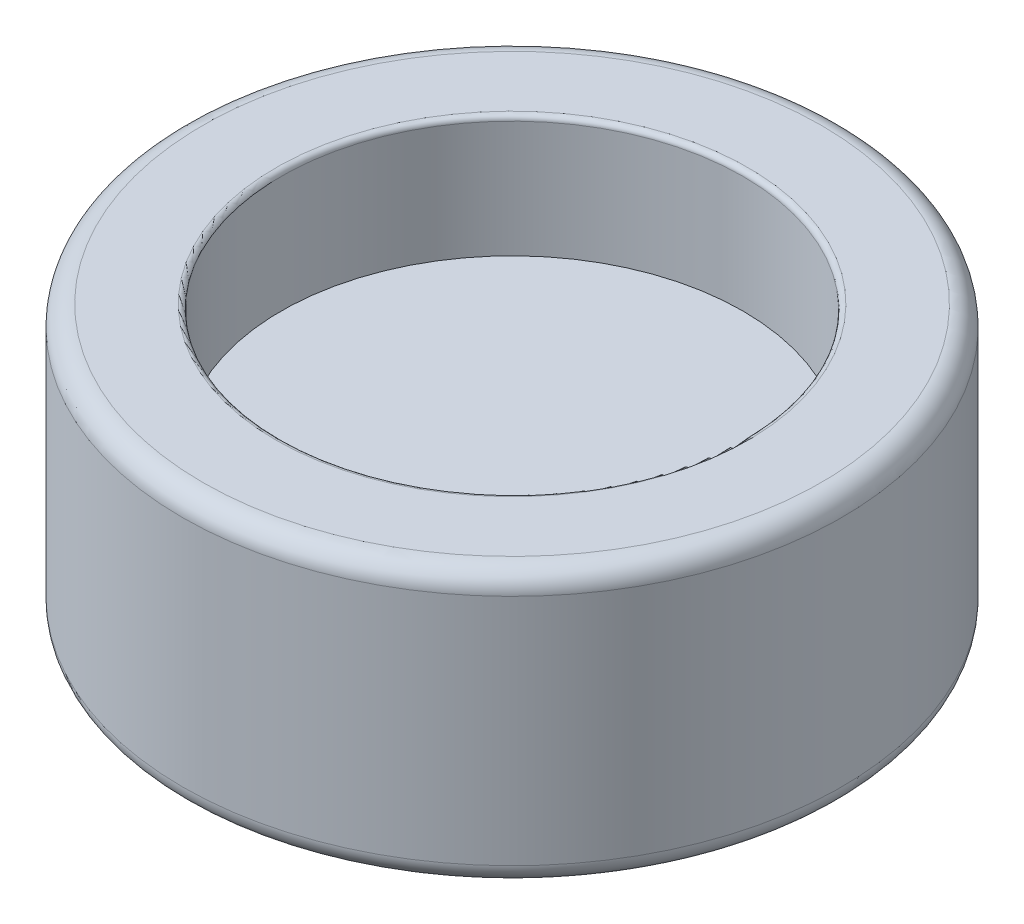
SolidWorks part; units mm, degrees
ref_plane "前视基准面" through (0, 0, 0) normal (0, 0, 1) x (1, 0, 0)
ref_plane "上视基准面" through (0, 0, 0) normal (0, 1, 0) x (1, 0, 0)
ref_plane "右视基准面" through (0, 0, 0) normal (1, 0, 0) x (0, 0, -1)
sketch "草图1" plane through (0, 0, 0) normal (0, 1, 0) x (1, 0, 0)
  circle A0 centre (0, 0) radius 32.5
  circle A1 centre (0, 0) radius 22.779
  dimension "D1" = 65
extrude "凸台-拉伸1" add sketch "草图1" along normal blind 27
fillet "圆角1" radius 2 2 edges at (0, 27, 32.5) (0, 0, 32.5)
fillet "圆角2" radius 0.5 2 edges at (0, 27, 22.779) (0, 0, 22.779)
extrude "凸台-拉伸2" add sketch "草图1<3>" along normal blind 15 contours A1
sketch "草图1<3>" plane through (0, 0, 0) normal (0, 1, 0) x (1, 0, 0) same geometry as "草图1"
